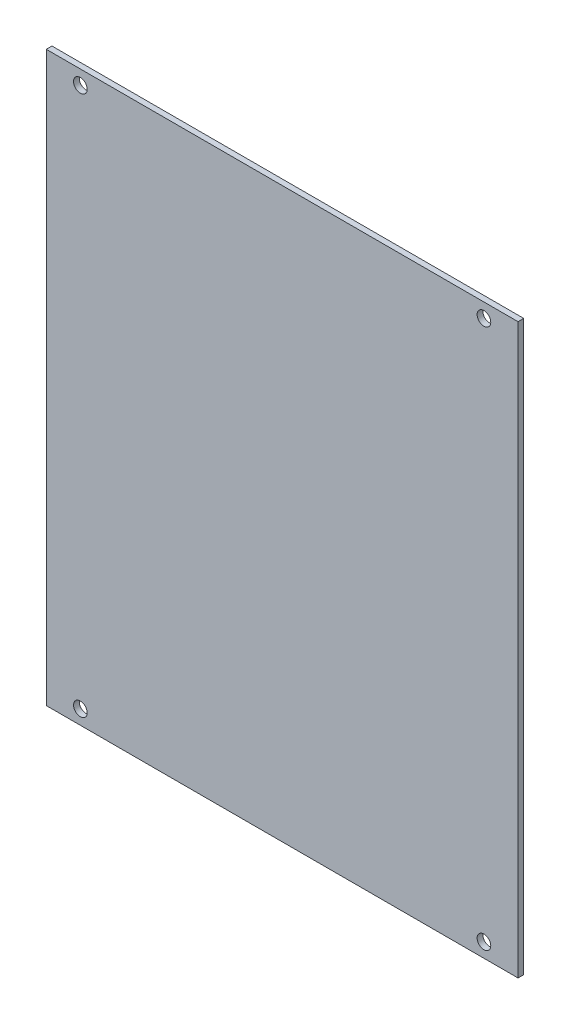
SolidWorks part; units mm, degrees
material "6061 Alloy"
ref_plane "Frontal" through (0, 0, 0) normal (0, 0, 1) x (1, 0, 0)
ref_plane "Superior" through (0, 0, 0) normal (0, 1, 0) x (1, 0, 0)
ref_plane "Direito" through (0, 0, 0) normal (1, 0, 0) x (0, 0, -1)
sketch "Sketch1" plane through (0, 0, 0) normal (0, 0, 1) x (1, 0, 0)
  line L1 (-41.5, -50) -> (41.5, -50)
  line L2 (-41.5, -50) -> (-41.5, 50)
  line L3 (-41.5, 50) -> (41.5, 50)
  line L4 (41.5, -50) -> (41.5, 50)
  line L5 (-41.5, -50) -> (41.5, 50) construction
  line L6 (-41.5, 50) -> (41.5, -50) construction
  point P0 (0, 0)
  dimension "D1" = 100
  dimension "D2" = 83
extrude "Boss-Extrude1" add sketch "Sketch1" along normal mid plane 1
hole_wizard "M2 Hole1 - A" positions "Sketch3" profile "Sketch2" hole size "M2" standard "DIN" end condition through all
sketch "Sketch3" plane through (0, 0, 0.5) normal (0, 0, 1) x (1, 0, 0)
  line L0 (41.5, 50) -> (-41.5, 50) construction
  line L1 (-41.5, 50) -> (-41.5, -50) construction
  line L2 (41.5, -50) -> (41.5, 50) construction
  line L3 (-41.5, -50) -> (41.5, -50) construction
  point P0 (-35.5, 47.5)
  point P2 (35.5, 47.5)
  point P4 (-35.5, -47.5)
  point P6 (35.5, -47.5)
  point P20 (-35.5, -47.5)
  point P22 (35.5, -47.5)
  dimension "D1" = 2.5
  dimension "D2" = 6
  dimension "D3" = 6
  dimension "D4" = 2.5
  dimension "D5" = 95
sketch "Sketch2" plane through (-35.5, 47.5, 0.5) normal (1, 0, 0) x (0, -1, 0)
  line L0 (0, 0) -> (0, 1)
  line L1 (0, 1) -> (1.2, 1)
  line L2 (1.2, 1) -> (1.2, 0)
  line L5 (1.2, 0) -> (0, 0)
  line L11 (0, -6.35) -> (0, 107.95) construction
  dimension "Thru Hole Dia." = 2.4
  dimension "Thru Hole Depth" = 1
